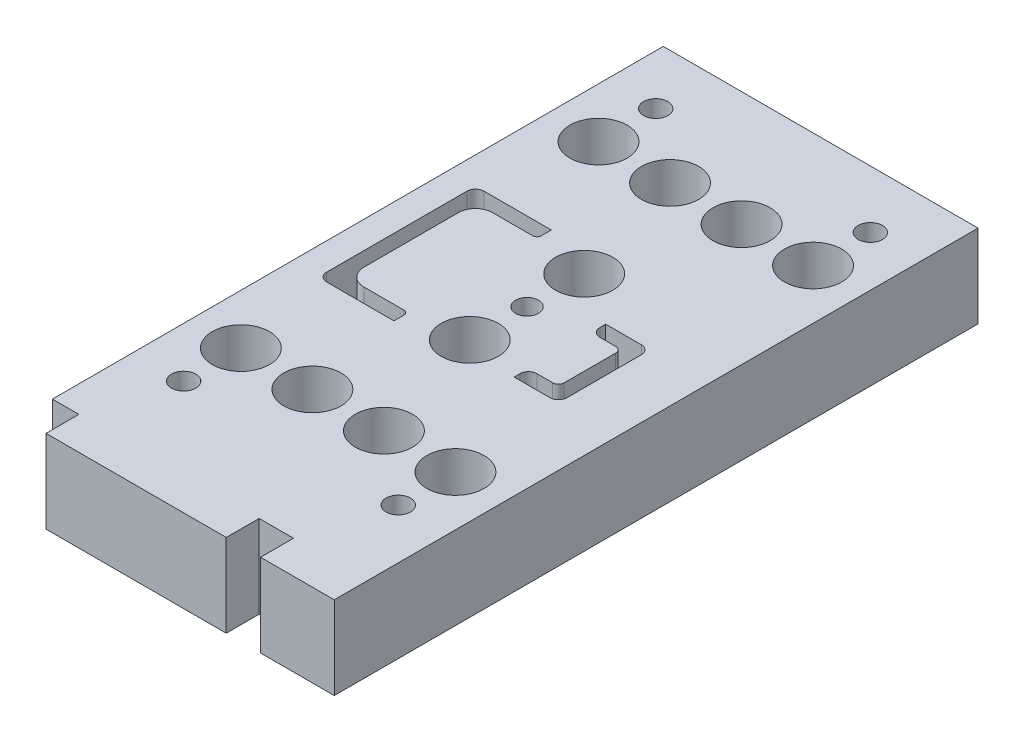
SolidWorks part; units mm, degrees
material "Plain Carbon Steel"
ref_plane "Front Plane" through (0, 0, 0) normal (0, 0, 1) x (1, 0, 0)
ref_plane "Top Plane" through (0, 0, 0) normal (0, 1, 0) x (1, 0, 0)
ref_plane "Right Plane" through (0, 0, 0) normal (1, 0, 0) x (0, 0, -1)
sketch "Sketch1" plane through (0, 0, 0) normal (0, 1, 0) x (1, 0, 0)
  line L1 (-55, -112.5) -> (55, -112.5)
  line L2 (-55, -112.5) -> (-55, 112.5)
  line L3 (-55, 112.5) -> (55, 112.5)
  line L4 (55, -112.5) -> (55, 112.5)
  line L5 (-55, -112.5) -> (55, 112.5) construction
  line L6 (-55, 112.5) -> (55, -112.5) construction
  point P0 (0, 0)
  dimension "D1" = 110
  dimension "D2" = 225
extrude "Boss-Extrude1" add sketch "Sketch1" against normal blind 29
sketch "Sketch2" plane through (0, 0, 0) normal (0, 1, 0) x (1, 0, 0)
  line L0 (-19, 37.36) -> (-19, 33.86) construction
  line L1 (-42.5, 37.36) -> (-19, 37.36) construction
  line L2 (-45.5, 34.36) -> (-45.5, -14.64) construction
  line L3 (-42.5, -17.64) -> (-19, -17.64) construction
  line L4 (-19, -17.64) -> (-19, -14.14) construction
  line L5 (-34.5, -12.64) -> (-20.5, -12.64) construction
  line L6 (-40.5, 26.36) -> (-40.5, -6.64) construction
  line L7 (-20.5, 32.36) -> (-34.5, 32.36) construction
  line L8 (-19, 37.36) -> (-19, 33.86)
  line L9 (-42.5, 37.36) -> (-19, 37.36)
  line L10 (-45.5, 34.36) -> (-45.5, -14.64)
  line L11 (-42.5, -17.64) -> (-19, -17.64)
  line L12 (-19, -17.64) -> (-19, -14.14)
  line L13 (-34.5, -12.64) -> (-20.5, -12.64)
  line L14 (-40.5, 26.36) -> (-40.5, -6.64)
  line L15 (-20.5, 32.36) -> (-34.5, 32.36)
  arc A0 (-20.5, 32.36) -> (-19, 33.86) centre (-20.5, 33.86) ccw construction
  arc A1 (-42.5, 37.36) -> (-45.5, 34.36) centre (-42.5, 34.36) ccw construction
  arc A2 (-45.5, -14.64) -> (-42.5, -17.64) centre (-42.5, -14.64) ccw construction
  arc A3 (-19, -14.14) -> (-20.5, -12.64) centre (-20.5, -14.14) ccw construction
  arc A4 (-40.5, -6.64) -> (-34.5, -12.64) centre (-34.5, -6.64) ccw construction
  arc A5 (-34.5, 32.36) -> (-40.5, 26.36) centre (-34.5, 26.36) ccw construction
  arc A6 (-20.5, 32.36) -> (-19, 33.86) centre (-20.5, 33.86) ccw
  arc A7 (-42.5, 37.36) -> (-45.5, 34.36) centre (-42.5, 34.36) ccw
  arc A8 (-45.5, -14.64) -> (-42.5, -17.64) centre (-42.5, -14.64) ccw
  arc A9 (-19, -14.14) -> (-20.5, -12.64) centre (-20.5, -14.14) ccw
  arc A10 (-40.5, -6.64) -> (-34.5, -12.64) centre (-34.5, -6.64) ccw
  arc A11 (-34.5, 32.36) -> (-40.5, 26.36) centre (-34.5, 26.36) ccw
extrude "Cut-Extrude1" cut sketch "Sketch2" against normal up to next
sketch "Sketch3" plane through (0, 0, 0) normal (0, 1, 0) x (1, 0, 0)
  line L0 (19, 18.36) -> (31.5, 18.36) construction
  line L1 (19, 18.36) -> (19, 16.36) construction
  line L2 (27.5, 13.36) -> (22, 13.36) construction
  line L3 (29.5, -6.64) -> (29.5, 11.36) construction
  line L4 (22, -8.64) -> (27.5, -8.64) construction
  line L5 (19, -13.64) -> (19, -11.64) construction
  line L6 (31.5, -13.64) -> (19, -13.64) construction
  line L7 (34.5, 15.36) -> (34.5, -10.64) construction
  line L8 (19, 18.36) -> (31.5, 18.36)
  line L9 (19, 18.36) -> (19, 16.36)
  line L10 (27.5, 13.36) -> (22, 13.36)
  line L11 (29.5, -6.64) -> (29.5, 11.36)
  line L12 (22, -8.64) -> (27.5, -8.64)
  line L13 (19, -13.64) -> (19, -11.64)
  line L14 (31.5, -13.64) -> (19, -13.64)
  line L15 (34.5, 15.36) -> (34.5, -10.64)
  arc A0 (34.5, 15.36) -> (31.5, 18.36) centre (31.5, 15.36) ccw construction
  arc A1 (19, 16.36) -> (22, 13.36) centre (22, 16.36) ccw construction
  arc A2 (29.5, 11.36) -> (27.5, 13.36) centre (27.5, 11.36) ccw construction
  arc A3 (27.5, -8.64) -> (29.5, -6.64) centre (27.5, -6.64) ccw construction
  arc A4 (22, -8.64) -> (19, -11.64) centre (22, -11.64) ccw construction
  arc A5 (31.5, -13.64) -> (34.5, -10.64) centre (31.5, -10.64) ccw construction
  arc A6 (34.5, 15.36) -> (31.5, 18.36) centre (31.5, 15.36) ccw
  arc A7 (19, 16.36) -> (22, 13.36) centre (22, 16.36) ccw
  arc A8 (29.5, 11.36) -> (27.5, 13.36) centre (27.5, 11.36) ccw
  arc A9 (27.5, -8.64) -> (29.5, -6.64) centre (27.5, -6.64) ccw
  arc A10 (22, -8.64) -> (19, -11.64) centre (22, -11.64) ccw
  arc A11 (31.5, -13.64) -> (34.5, -10.64) centre (31.5, -10.64) ccw
extrude "Cut-Extrude2" cut sketch "Sketch3" against normal up to next
sketch "Sketch4" plane through (0, -29, 0) normal (0, -1, 0) x (1, 0, 0)
  circle A0 centre (0, 100) radius 8.5
  circle A1 centre (0, -100) radius 8.5
  dimension "D1" = 17
extrude "Cut-Extrude3" cut sketch "Sketch4" against normal blind 5
sketch "Sketch5" plane through (0, 0, 0) normal (0, 1, 0) x (1, 0, 0)
  line L2 (-55, 112.5) -> (-55, -112.5) construction
  line L5 (-19, 37.36) -> (-42.5, 37.36) construction
  line L6 (-40.5, 9.86) -> (29.5, 9.86) construction
  line L7 (-40.5, -6.64) -> (-40.5, 26.36) construction
  line L9 (29.5, 11.36) -> (29.5, -6.64) construction
  circle A0 centre (-37.5, 72.36) radius 10
  circle A1 centre (-12.5, 72.36) radius 10
  circle A2 centre (12.5, 72.36) radius 10
  circle A3 centre (37.5, 72.36) radius 10
  circle A4 centre (37.5, -52.64) radius 10
  circle A5 centre (12.5, -52.64) radius 10
  circle A6 centre (-12.5, -52.64) radius 10
  circle A7 centre (-37.5, -52.64) radius 10
  circle A8 centre (0, 29.86) radius 10
  circle A9 centre (0, -10.14) radius 10
  dimension "D1" = 20
  dimension "D2" = 17.5
  dimension "D3" = 35
  dimension "D5" = 25
  dimension "D6" = 20
  dimension "D7" = 20
  dimension "D4" = 4
extrude "Cut-Extrude4" cut sketch "Sketch5" against normal blind 17
sketch "Sketch6" plane through (0, 0, 0) normal (0, 1, 0) x (1, 0, 0)
  line L0 (-55, -112.5) -> (55, -112.5) construction
  line L1 (29.25, -112.5) -> (17.25, -112.5)
  line L2 (29.25, -112.5) -> (29.25, -101)
  line L3 (29.25, -101) -> (17.25, -101)
  line L4 (17.25, -112.5) -> (17.25, -101)
  line L5 (18.75, -102) -> (27.75, -102) construction
  line L6 (-45.75, -112.5) -> (-57.75, -112.5)
  line L7 (-45.75, -112.5) -> (-45.75, -101)
  line L8 (-45.75, -101) -> (-57.75, -101)
  line L9 (-57.75, -112.5) -> (-57.75, -101)
  line L10 (28.25, -102.5) -> (28.25, -115) construction
  line L11 (18.25, -115) -> (18.25, -102.5) construction
  line L12 (-56.75, -115) -> (-56.75, -102.5) construction
  line L13 (-46.75, -102.5) -> (-46.75, -115) construction
  line L14 (-56.25, -102) -> (-47.25, -102) construction
  dimension "D1" = 1
  dimension "D2" = 1
  dimension "D3" = 1
  dimension "D4" = 1
  dimension "D5" = 1
  dimension "D6" = 1
extrude "Cut-Extrude5" cut sketch "Sketch6" against normal up to next
hole_wizard "M10 Tapped Hole1" positions "Sketch9" profile "Sketch8" tap size "M10" standard "ISO" end condition through all
sketch "Sketch9" plane through (0, 0, 0) normal (0, 1, 0) x (1, 0, 0)
  line L2 (-37.5, 72.36) -> (-37.5, 92.36) construction
  line L4 (37.5, 72.36) -> (37.5, 92.36) construction
  circle A1 centre (-37.5, 72.36) radius 10 construction
  circle A2 centre (-37.5, -52.64) radius 10 construction
  point P0 (-37.5, -72.64)
  point P2 (37.5, -72.64)
  point P4 (37.5, 92.36)
  point P6 (-37.5, 92.36)
  dimension "D1" = 20
  dimension "D2" = 20
sketch "Sketch8" plane through (-37.5, 0, 72.64) normal (1, 0, 0) x (0, 0, 1)
  line L0 (0, 0) -> (0, 29)
  line L1 (0, 29) -> (4.25, 29)
  line L2 (4.25, 29) -> (4.25, 0)
  line L5 (4.25, 0) -> (0, 0)
  line L11 (0, -6.35) -> (0, 107.95) construction
  dimension "Thru Tap Drill Dia." = 8.5
  dimension "Thru Tap Drill Depth" = 29
cosmetic thread "Hole Thread1" parameters "D2"=10
cosmetic thread "Hole Thread2" parameters "D2"=10
cosmetic thread "Hole Thread3" parameters "D2"=10
cosmetic thread "Hole Thread4" parameters "D2"=10
sketch "Sketch10" plane through (0, 0, 0) normal (0, 1, 0) x (1, 0, 0)
  circle A0 centre (0, 9.86) radius 5 construction
  circle A1 centre (0, 9.86) radius 5 construction
  circle A2 centre (0, 9.86) radius 4
  dimension "D1" = 8
extrude "Cut-Extrude6" cut sketch "Sketch10" against normal up to next
